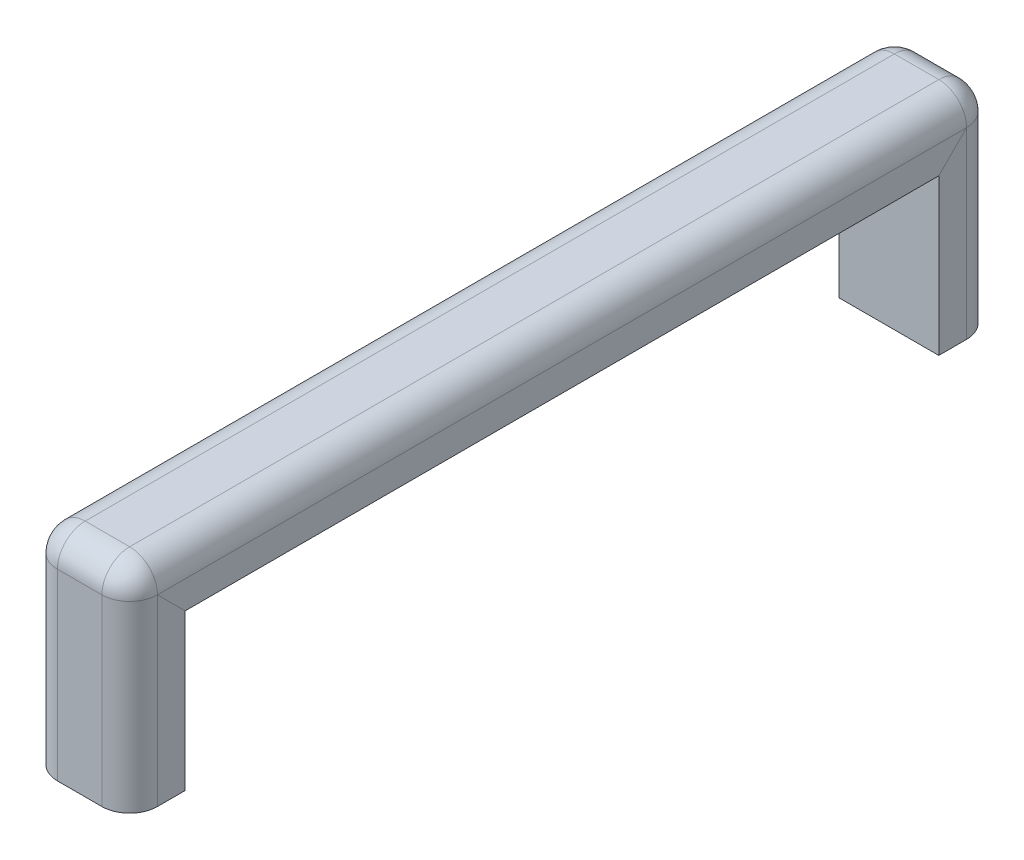
SolidWorks part; units mm, degrees
material "6061-T6 (SS)"
ref_plane "Front Plane" through (0, 0, 0) normal (0, 0, 1) x (1, 0, 0)
ref_plane "Top Plane" through (0, 0, 0) normal (0, 1, 0) x (1, 0, 0)
ref_plane "Right Plane" through (0, 0, 0) normal (1, 0, 0) x (0, 0, -1)
sketch "Sketch1" plane through (0, 0, 0) normal (1, 0, 0) x (0, 0, -1)
  line L0 (-430.7522, -177.8635) -> (-430.7522, 0)
  line L1 (-430.7522, 0) -> (430.7522, 0)
  line L2 (430.7522, 0) -> (430.7523, -177.8635)
  line L3 (-409.4162, -21.336) -> (409.4162, -21.336) construction
  line L4 (409.4162, -21.336) -> (409.4162, -177.8635) construction
  line L5 (409.4162, -21.336) -> (409.4162, 0) construction
  line L6 (0, 0) -> (0, -152.4) construction
  line L7 (409.4162, -21.336) -> (430.7522, -21.336) construction
  line L8 (-409.4162, -21.336) -> (-409.4162, -177.8635) construction
  point P5 (0, 0)
  point P15 (0, -21.336)
  dimension "D3" = 21.336
  dimension "D1" = 818.8325
  dimension "D2" = 156.5275
sketch "Sketch2" plane through (0, 0, 0) normal (0, 1, 0) x (1, 0, 0)
  line L0 (0, -430.7522) -> (114.3, -430.7522)
  line L2 (114.3, -430.7522) -> (114.3, -462.5022)
  line L3 (82.55, -494.2522) -> (31.75, -494.2522)
  line L4 (0, -430.7522) -> (0, 430.7522) construction
  line L5 (0, -462.5022) -> (0, -430.7522)
  arc A0 (114.3, -462.5022) -> (82.55, -494.2522) centre (82.55, -462.5022) cw
  arc A2 (31.75, -494.2522) -> (0, -462.5022) centre (31.75, -462.5022) cw
  dimension "D3" = 31.75
  dimension "D1" = 63.5
  dimension "D2" = 114.3
sweep "Sweep2" add profiles "Sketch2" path "Sketch1"
fillet "Fillet1" radius 31.75 6 edges at (105.0006, 54.2006, 484.9529) (9.2994, 54.2006, 484.9529) (105.0006, 54.2006, -484.9529) (9.2994, 54.2006, -484.9529) (57.15, 63.5, 494.2522) (57.15, 63.5, -494.2522)
equation "\"D1@Sketch1\"=32.175in+1/16"
equation "\"D2@Sketch1\"=6.100in+1/16"
